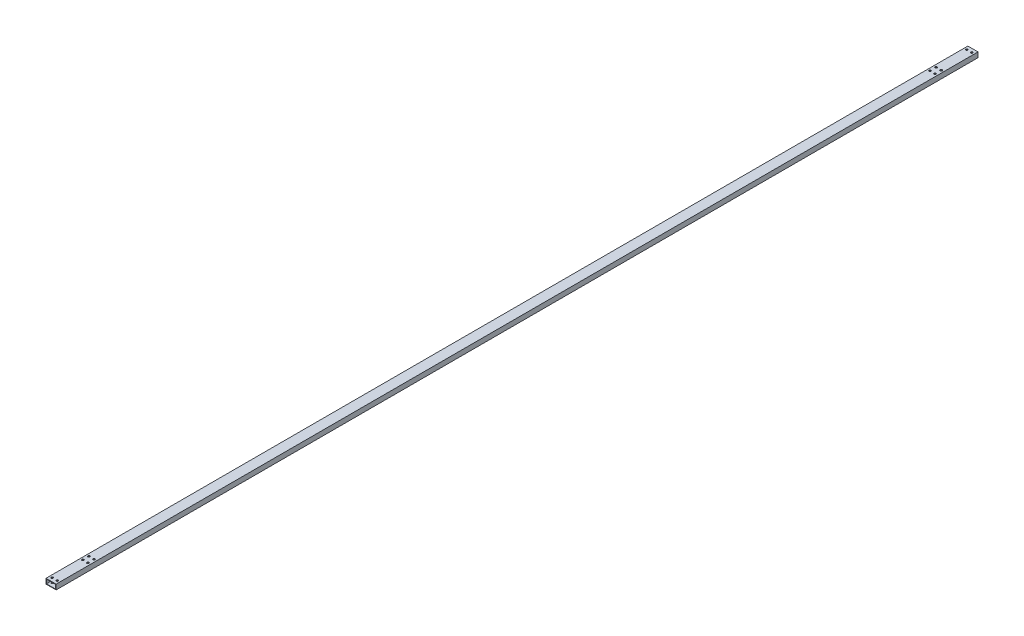
SolidWorks part; units mm, degrees
material "1100-H18 棒材(SS)"
ref_plane "前视基准面" through (0, 0, 0) normal (0, 0, 1) x (1, 0, 0)
ref_plane "上视基准面" through (0, 0, 0) normal (0, 1, 0) x (1, 0, 0)
ref_plane "右视基准面" through (0, 0, 0) normal (1, 0, 0) x (0, 0, -1)
other "Configuration Table"
sketch "草图1" plane through (0, 0, 0) normal (0, 0, 1) x (1, 0, 0)
  line L1 (0, 0) -> (20, 0)
  line L2 (0, 0) -> (0, 10)
  line L3 (0, 10) -> (20, 10)
  line L4 (20, 0) -> (20, 10)
  line L5 (1, 1) -> (19, 1)
  line L6 (1, 1) -> (1, 9)
  line L7 (1, 9) -> (19, 9)
  line L8 (19, 1) -> (19, 9)
  dimension "D1" = 20
  dimension "D2" = 10
  dimension "D3" = 1
  dimension "D4" = 1
  dimension "D5" = 1
  dimension "D6" = 1
extrude "凸台-拉伸1" add sketch "草图1" along normal blind 1820
sketch "草图2" plane through (0, 0, 0) normal (0, -1, 0) x (1, 0, 0)
  line L0 (10, -105.5691) -> (10, 473.4318) construction
  circle A0 centre (10, 284.5291) radius 1.7 construction
  circle A1 centre (10, 153.2041) radius 1.7 construction
  circle A2 centre (10, 284.5291) radius 1.7
  circle A3 centre (10, 153.2041) radius 1.7
  circle A4 centre (10, 535.8541) radius 1.7 construction
  circle A5 centre (10, 404.5291) radius 1.7 construction
  circle A6 centre (10, 535.8541) radius 1.7
  circle A7 centre (10, 404.5291) radius 1.7
  circle A9 centre (10, 655.8541) radius 1.7 construction
  circle A11 centre (10, 655.8541) radius 1.7
  circle A12 centre (10, 787.1791) radius 1.7 construction
  circle A13 centre (10, 787.1791) radius 1.7
  circle A14 centre (10, 907.1791) radius 1.7 construction
  circle A15 centre (10, 907.1791) radius 1.7
  circle A16 centre (10, 1038.5041) radius 1.7 construction
  circle A17 centre (10, 1038.5041) radius 1.7
  circle A18 centre (10, 1158.5041) radius 1.7 construction
  circle A19 centre (10, 1158.5041) radius 1.7
  circle A20 centre (10, 1289.8291) radius 1.7 construction
  circle A21 centre (10, 1289.8291) radius 1.7
  circle A22 centre (10, 1409.8291) radius 1.7 construction
  circle A23 centre (10, 1409.8291) radius 1.7
  circle A24 centre (10, 910.4327) radius 1.7 construction
  circle A25 centre (10, 910.4327) radius 1.7
  circle A26 centre (10, 790.4327) radius 1.7 construction
  circle A27 centre (10, 790.4327) radius 1.7
  circle A28 centre (10, 118.2041) radius 1.7
  dimension "D1" = 35
extrude "切除-拉伸1" cut sketch "草图2" against normal through all rebuild error yes
sketch "草图3" plane through (0, 0, 0) normal (0, -1, 0) x (1, 0, 0)
  circle A1 centre (5, 1812.8) radius 2
  circle A2 centre (5, 1812.8) radius 2
  circle A3 centre (15, 1812.8) radius 2
  circle A4 centre (15, 1812.8) radius 2
  circle A5 centre (15, 1752.2) radius 2
  circle A6 centre (15, 1752.2) radius 2
  circle A7 centre (15, 1740.2) radius 2
  circle A8 centre (15, 1740.2) radius 2
  circle A9 centre (5, 1740.2) radius 2
  circle A10 centre (5, 1740.2) radius 2
  circle A11 centre (5, 1752.2) radius 2
  circle A12 centre (5, 1752.2) radius 2
  circle A13 centre (5, 7.2) radius 2
  circle A14 centre (5, 7.2) radius 2
  circle A15 centre (15, 7.2) radius 2
  circle A16 centre (15, 7.2) radius 2
  circle A17 centre (15, 67.8) radius 2
  circle A18 centre (15, 67.8) radius 2
  circle A19 centre (15, 79.8) radius 2
  circle A20 centre (15, 79.8) radius 2
  circle A21 centre (5, 79.8) radius 2
  circle A22 centre (5, 79.8) radius 2
  circle A23 centre (5, 67.8) radius 2
  circle A24 centre (5, 67.8) radius 2
  dimension "D1" = 0
  dimension "D2" = 0
  dimension "D3" = 0
  dimension "D4" = 0
  dimension "D5" = 0
  dimension "D6" = 0
  dimension "D7" = 0
  dimension "D8" = 0
  dimension "D9" = 0
  dimension "D10" = 0
  dimension "D11" = 0
  dimension "D12" = 0
extrude "切除-拉伸2" cut sketch "草图3" against normal through all
